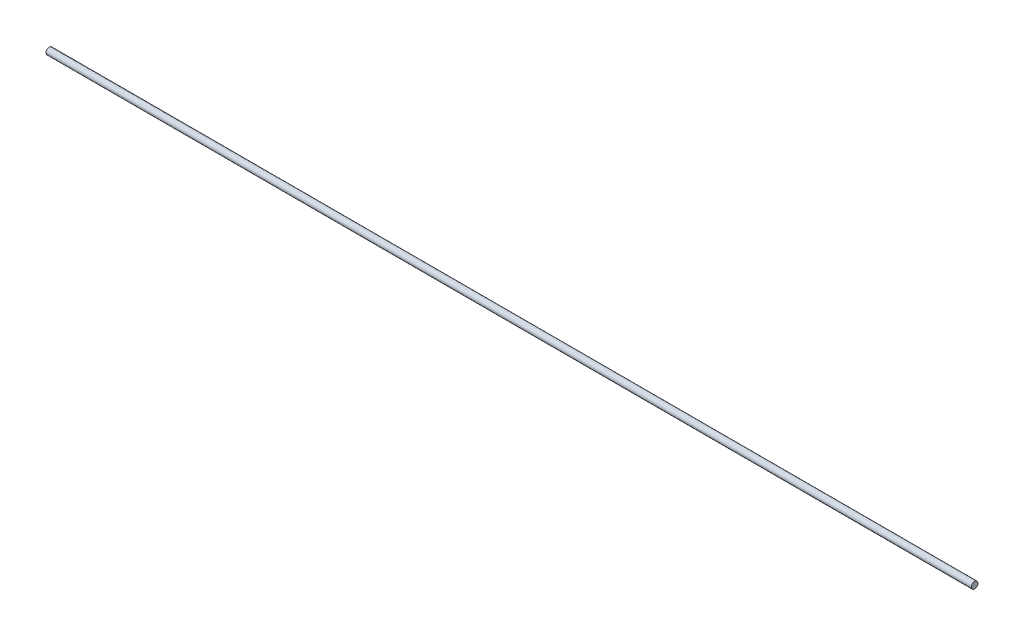
SolidWorks part; units mm, degrees
material "Glass"
ref_plane "Front Plane" through (0, 0, 0) normal (0, 0, 1) x (1, 0, 0)
ref_plane "Top Plane" through (0, 0, 0) normal (0, 1, 0) x (1, 0, 0)
ref_plane "Right Plane" through (0, 0, 0) normal (1, 0, 0) x (0, 0, -1)
sketch "Sketch1" plane through (0, 0, 0) normal (1, 0, 0) x (0, 0, -1)
  circle A0 centre (0, 0) radius 1
  dimension "D1" = 2
extrude "Boss-Extrude1" add sketch "Sketch1" along normal blind 280
